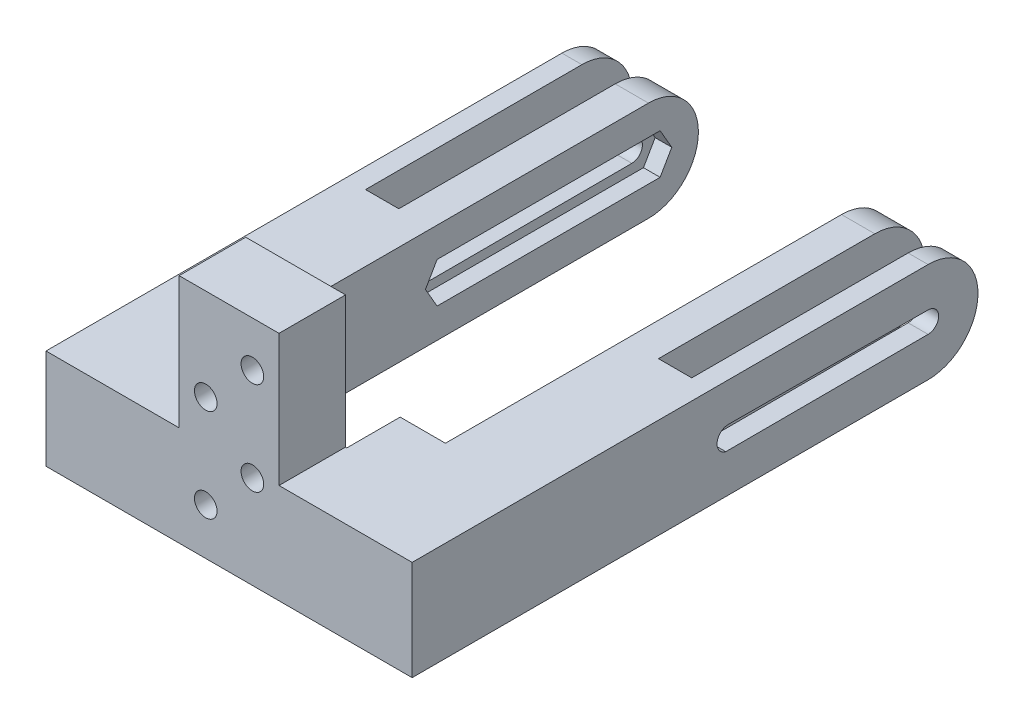
SolidWorks part; units mm, degrees
ref_plane "前视基准面" through (0, 0, 0) normal (0, 0, 1) x (1, 0, 0)
ref_plane "上视基准面" through (0, 0, 0) normal (0, 1, 0) x (1, 0, 0)
ref_plane "右视基准面" through (0, 0, 0) normal (1, 0, 0) x (0, 0, -1)
sketch "Sketch1" plane through (0, 0, 0) normal (0, 1, 0) x (1, 0, 0)
  line L0 (-27.5, 0) -> (27.5, 0)
  line L1 (-27.5, 0) -> (-27.5, 85)
  line L2 (-27.5, 85) -> (-14.5, 85)
  line L3 (-14.5, 85) -> (-14.5, 18)
  line L4 (0, 10) -> (0, 0) construction
  line L5 (14.5, 18) -> (14.5, 85)
  line L6 (14.5, 85) -> (27.5, 85)
  line L7 (27.5, 85) -> (27.5, 0)
  line L8 (7.7, 18) -> (-7.7, 18) construction
  line L9 (14.5, 18) -> (7.7, 18)
  line L10 (7.7, 18) -> (7.7, 10)
  line L12 (7.7, 10) -> (-7.7, 10)
  line L14 (-7.7, 10) -> (-7.7, 18)
  line L15 (-7.7, 18) -> (-14.5, 18)
  dimension "D1" = 85
  dimension "D2" = 13
  dimension "D3" = 29
  dimension "D4" = 8
  dimension "D5" = 18
  dimension "D6" = 15.4
extrude "Boss-Extrude1" add sketch "Sketch1" along normal blind 15
sketch "Sketch2" plane through (0, 15, 0) normal (0, 1, 0) x (1, 0, 0)
  line L0 (-7.5, 0) -> (7.5, 0)
  line L1 (-27.5, 0) -> (27.5, 0) construction
  line L2 (-7.5, 0) -> (-7.5, 10)
  line L4 (-7.5, 10) -> (7.5, 10)
  line L5 (7.5, 10) -> (7.5, 0)
  line L6 (7.7, 10) -> (-7.7, 10) construction
  dimension "D1" = 15
extrude "Boss-Extrude2" add sketch "Sketch2" along normal blind 19.8
sketch "Sketch3" plane through (0, 0, -85) normal (0, 0, -1) x (-1, 0, 0)
  line L0 (19.5, 15) -> (19.5, 0)
  line L1 (0, 0) -> (0, 34.8) construction
  line L2 (-27.5, 15) -> (-14.5, 15) construction
  line L3 (-24.5, 15) -> (-19.5, 15)
  line L4 (-24.5, 15) -> (-24.5, 0)
  line L5 (-24.5, 0) -> (-19.5, 0)
  line L6 (-7.5, 34.8) -> (7.5, 34.8) construction
  line L7 (-19.5, 15) -> (-19.5, 0)
  line L8 (-27.5, 0) -> (-14.5, 0) construction
  line L9 (24.5, 0) -> (19.5, 0)
  line L10 (24.5, 15) -> (24.5, 0)
  line L11 (24.5, 15) -> (19.5, 15)
  line L12 (-27.5, 15) -> (-27.5, 0) construction
  dimension "D1" = 5
  dimension "D2" = 3
extrude "Cut-Extrude1" cut sketch "Sketch3" against normal blind 40
sketch "Sketch4" plane through (0, 0, -10) normal (0, 0, -1) x (-1, 0, 0)
  line L0 (-7.5, 34.8) -> (7.5, 34.8) construction
  line L1 (-3.5, 34.8) -> (3.5, 34.8) construction
  line L2 (-3.5, 34.8) -> (-3.5, 28) construction
  line L3 (-3.5, 28) -> (3.5, 28) construction
  line L4 (3.5, 28) -> (3.5, 21) construction
  circle A0 centre (-3.5, 28) radius 1.7
  circle A1 centre (3.5, 21) radius 1.7
  point P0 (0, 34.8)
  dimension "D1" = 7
extrude "Cut-Extrude2" cut sketch "Sketch4" against normal up to next
pattern_linear "LPattern1" count 2 spacing 14 along (0, -1, 0) of "Cut-Extrude2"
sketch "Sketch5" plane through (14.5, 0, 0) normal (-1, 0, 0) x (0, 0, 1)
  line L0 (-85, 7.5) -> (-77.5, 7.5) construction
  line L1 (-79.25, 10.5311) -> (-45.75, 10.5311)
  line L2 (-79.25, 4.4689) -> (-45.75, 4.4689)
  line L3 (-79.25, 10.5311) -> (-81, 7.5)
  line L4 (-81, 7.5) -> (-79.25, 4.4689)
  line L5 (-77.5, 7.5) -> (-47.5, 7.5) construction
  line L7 (-85, 15) -> (-85, 0) construction
  line L8 (-85, 15) -> (-85, 0) construction
  line L10 (-44, 7.5) -> (-45.75, 10.5311)
  line L15 (-45.75, 4.4689) -> (-44, 7.5)
  line L16 (-75.5194, 10.5311) -> (-79.0088, 10.5311) [skipped]
  line L17 (-73.8847, 7.3003) -> (-75.6294, 10.3222) [skipped]
  line L18 (-75.8653, 4.2692) -> (-74.1206, 7.2911) [skipped]
  line L19 (-79.4806, 4.4689) -> (-75.9912, 4.4689) [skipped]
  circle A0 centre (-77.5, 7.5) radius 3.0311 construction
  circle A1 centre (-47.5, 7.5) radius 3.0311 construction
  dimension "D1" = 7.5
  dimension "D2" = 3.5
  dimension "D3" = 30
extrude "Cut-Extrude3" cut sketch "Sketch5" against normal blind 2.5
sketch "Sketch6" plane through (17, 0, 0) normal (-1, 0, 0) x (0, 0, 1)
  line L0 (-45.75, 4.4689) -> (-47.5, 7.5) construction
  line L1 (-47.5, 7.5) -> (-44, 7.5) construction
  line L2 (-44, 7.5) -> (-45.75, 4.4689) construction
  line L3 (-79.25, 4.4689) -> (-77.5, 7.5) construction
  line L4 (-77.5, 7.5) -> (-81, 7.5) construction
  line L5 (-81, 7.5) -> (-79.25, 4.4689) construction
  line L6 (-77.5, 9.0881) -> (-47.5, 9.2)
  line L7 (-47.1161, 5.8439) -> (-77.5036, 5.9119)
  circle A0 centre (-47.5, 7.5) radius 1.7 construction
  circle A1 centre (-77.5, 7.5) radius 1.5881 construction
  arc A2 (-77.5, 9.0881) -> (-77.5036, 5.9119) centre (-77.5, 7.5) ccw
  arc A3 (-47.5, 9.2) -> (-47.1161, 5.8439) centre (-47.5, 7.5) cw
extrude "Cut-Extrude4" cut sketch "Sketch6" against normal blind 15
mirror "Mirror1" about plane through (0, 0, 0) normal (1, 0, 0) of "Cut-Extrude4", "Cut-Extrude3"
fillet "Fillet1" radius 7.5 8 edges at (26, 15, -85) (17, 15, -85) (-17, 15, -85) (-26, 15, -85) (26, 0, -85) (17, 0, -85) (-17, 0, -85) (-26, 0, -85)
